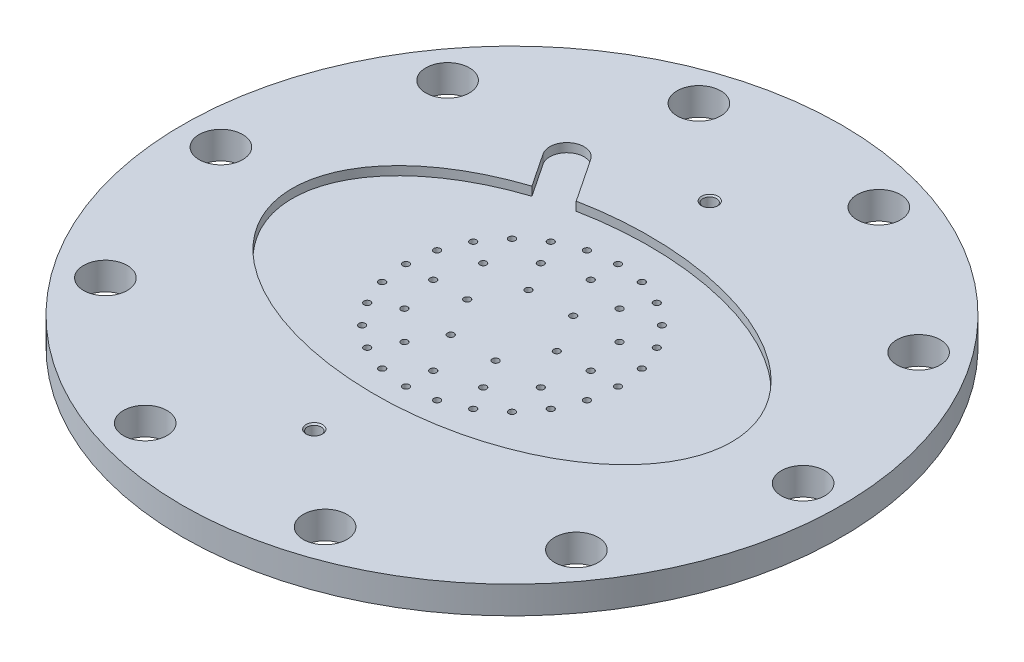
SolidWorks part; units mm, degrees
ref_plane "Front Plane" through (0, 0, 0) normal (0, 0, 1) x (1, 0, 0)
ref_plane "Top Plane" through (0, 0, 0) normal (0, 1, 0) x (1, 0, 0)
ref_plane "Right Plane" through (0, 0, 0) normal (1, 0, 0) x (0, 0, -1)
sketch "Sketch1" plane through (0, 0, 0) normal (0, 0, 1) x (1, 0, 0)
  line L0 (0, -6.35) -> (54.8259, -6.35)
  line L1 (0, 0) -> (76.2, 0)
  line L2 (0, 0) -> (0, -6.35)
  line L4 (76.2, 0) -> (76.2, -6.35)
  line L5 (54.8259, -6.35) -> (54.8259, -3.6576)
  line L6 (54.8259, -3.6576) -> (58.8899, -3.6576)
  line L7 (58.8899, -3.6576) -> (58.8899, -6.35)
  line L8 (58.8899, -6.35) -> (76.2, -6.35)
  dimension "D1" = 6.35
  dimension "D2" = 76.2
  dimension "D3" = 58.8899
  dimension "D4" = 4.064
  dimension "D5" = 2.6924
revolve "Revolve1" add sketch "Sketch1" angle 360 about L2
sketch "Sketch2" plane through (0, 0, 0) normal (0, 1, 0) x (1, 0, 0)
  line L0 (0, 0) -> (67.31, 0) construction
  dimension "D1" = 67.31
ref_axis "Axis1" through (0, 0.3175, 0) along (0, -1, 0)
hole_wizard "3/8 Clearance Hole1" positions "3DSketch2" profile "Sketch4" hole size "3/8" standard "ANSI Inch" end condition through all
sketch3d "3DSketch2"
  point P0 (67.31, 0, 0)
sketch "Sketch4" plane through (67.31, 0, 0) normal (1, 0, 0) x (0, 0, 1)
  line L0 (0, 0) -> (0, 6.35)
  line L1 (0, 6.35) -> (5.0419, 6.35)
  line L2 (5.0419, 6.35) -> (5.0419, 0)
  line L5 (5.0419, 0) -> (0, 0)
  line L11 (0, -6.35) -> (0, 107.95) construction
  dimension "Thru Hole Dia." = 10.0838
  dimension "Thru Hole Depth" = 6.35
pattern_circular "CirPattern1" count 10 over 360 about axis through (0, 0.3175, 0) along (0, -1, 0) of "3/8 Clearance Hole1"
sketch "Sketch5" plane through (0, 0, 0) normal (0, 1, 0) x (1, 0, 0)
  line L0 (-50.8, 0) -> (50.8, 0) construction
  line L1 (0, 0) -> (-25.4, 38.1) construction
  line L2 (-3.3022, -2.2015) -> (-28.7022, 35.8985)
  line L3 (3.3022, 2.2015) -> (-22.0978, 40.3015)
  arc A0 (-3.3022, -2.2015) -> (3.3022, 2.2015) centre (0, 0) ccw
  arc A1 (-22.0978, 40.3015) -> (-28.7022, 35.8985) centre (-25.4, 38.1) ccw
  ellipse E0 centre (0, 0) end of major axis (50.8, 0) minor radius 31.75
  point P10 (-12.7, 19.05)
  dimension "D5" = 3.9688
  dimension "D1" = 31.75
  dimension "D2" = 50.8
  dimension "D3" = 25.4
  dimension "D4" = 38.1
extrude "Cut-Extrude1" cut sketch "Sketch5" against normal blind 2.032 contours E0 | L3 A1 L2 A0
hole_wizard "1/8 (0.125) Diameter Hole1" positions "3DSketch3" profile "Sketch7" hole size "1/8" standard "ANSI Inch"
sketch3d "3DSketch3"
  line L0 (0, 0, 45.72) -> (0, 0, -45.72) construction
  point P15 (0, 0, 45.72)
  point P21 (0, 0, -45.72)
  dimension "D1" = 91.44
sketch "Sketch7" plane through (0, 0, -45.72) normal (1, 0, 0) x (0, 0, 1)
  line L0 (0, 0) -> (0, 3.81)
  line L1 (0, 3.81) -> (1.5875, 2.8561)
  line L2 (1.5875, 2.8561) -> (1.5875, 0.3175)
  line L3 (1.5875, 0.3175) -> (1.905, 0)
  line L5 (1.905, 0) -> (0, 0)
  line L6 (-1.5875, 0.3175) -> (-1.905, 0) construction
  line L10 (0, 3.81) -> (-1.5875, 2.8561) construction
  line L11 (0, -6.35) -> (0, 107.95) construction
  dimension "Hole Dia." = 3.175
  dimension "Hole Depth" = 3.81
  dimension "Near C'Sink Dia." = 3.81
  dimension "Near C'Sink Angle" = 90
  dimension "Drill Angle" = 118
sketch "Sketch8" plane through (0, -2.032, 0) normal (0, 1, 0) x (1, 0, 0)
  circle A0 centre (-10.3632, 0) radius 0.7557
  circle A1 centre (-18.2118, 0) radius 0.7556
  circle A2 centre (-24.511, 0) radius 0.7556
  circle A3 centre (-5.1816, 8.9748) radius 0.7556
  circle A4 centre (5.1816, 8.9748) radius 0.7556
  circle A5 centre (10.3632, 0) radius 0.7557
  circle A6 centre (5.1816, -8.9748) radius 0.7557
  circle A7 centre (-5.1816, -8.9748) radius 0.7556
  circle A8 centre (-15.7719, 9.1059) radius 0.7556
  circle A9 centre (-9.1059, 15.7719) radius 0.7556
  circle A10 centre (0, 18.2118) radius 0.7556
  circle A11 centre (9.1059, 15.7719) radius 0.7556
  circle A12 centre (15.7719, 9.1059) radius 0.7556
  circle A13 centre (18.2118, 0) radius 0.7556
  circle A14 centre (15.7719, -9.1059) radius 0.7556
  circle A15 centre (9.1059, -15.7719) radius 0.7556
  circle A16 centre (0, -18.2118) radius 0.7556
  circle A17 centre (-9.1059, -15.7719) radius 0.7556
  circle A18 centre (-15.7719, -9.1059) radius 0.7556
  circle A19 centre (-23.6758, 6.3439) radius 0.7556
  circle A20 centre (-21.2271, 12.2555) radius 0.7557
  circle A21 centre (-17.3319, 17.3319) radius 0.7556
  circle A22 centre (-12.2555, 21.2271) radius 0.7556
  circle A23 centre (-6.3439, 23.6758) radius 0.7556
  circle A24 centre (0, 24.511) radius 0.7556
  circle A25 centre (6.3439, 23.6758) radius 0.7556
  circle A26 centre (12.2555, 21.2271) radius 0.7556
  circle A27 centre (17.3319, 17.3319) radius 0.7556
  circle A28 centre (21.2271, 12.2555) radius 0.7556
  circle A29 centre (23.6758, 6.3439) radius 0.7556
  circle A30 centre (24.511, 0) radius 0.7556
  circle A31 centre (23.6758, -6.3439) radius 0.7557
  circle A32 centre (21.2271, -12.2555) radius 0.7556
  circle A33 centre (17.3319, -17.3319) radius 0.7556
  circle A34 centre (12.2555, -21.2271) radius 0.7556
  circle A35 centre (6.3439, -23.6758) radius 0.7556
  circle A36 centre (0, -24.511) radius 0.7556
  circle A37 centre (-6.3439, -23.6758) radius 0.7556
  circle A38 centre (-12.2555, -21.2271) radius 0.7556
  circle A39 centre (-17.3319, -17.3319) radius 0.7556
  circle A40 centre (-21.2271, -12.2555) radius 0.7556
  circle A41 centre (-23.6758, -6.3439) radius 0.7556
  point P19 (0, 0)
  point P42 (0, 0)
  point P89 (0, 0)
  dimension "D1" = 1.5113
  dimension "D2" = 1.5113
  dimension "D3" = 1.5113
  dimension "D4" = 10.3632
  dimension "D5" = 18.2118
  dimension "D6" = 24.511
  dimension "D7" = 6
  dimension "D8" = 12
  dimension "D9" = 24
extrude "Cut-Extrude2" cut sketch "Sketch8" against normal through all both and the other way through all
